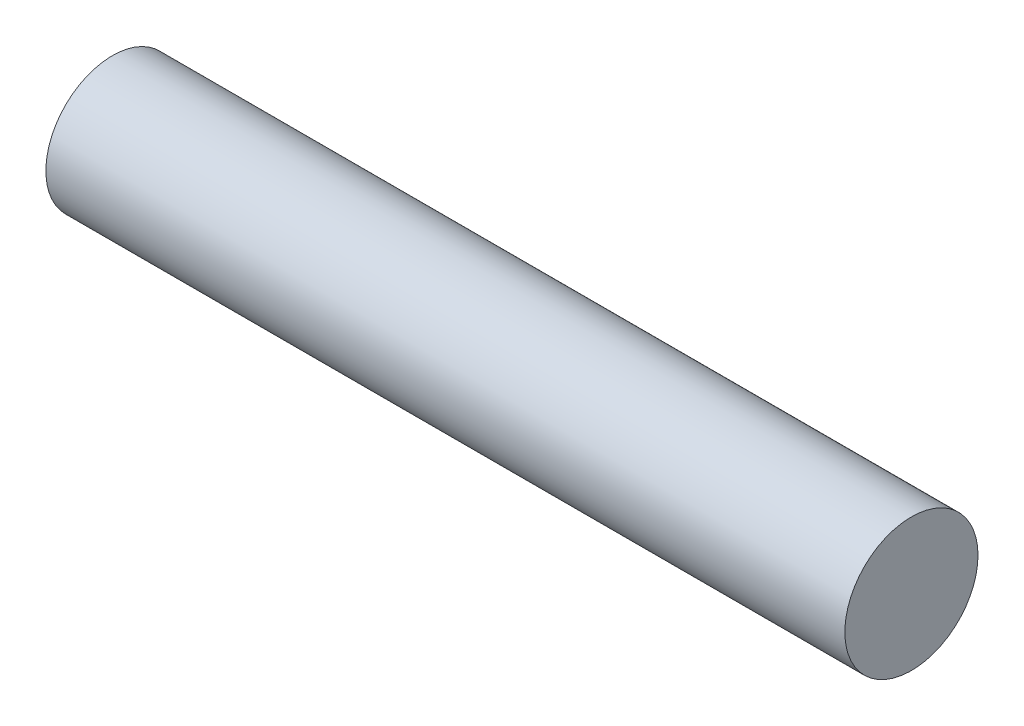
SolidWorks part; units mm, degrees
ref_plane "Front Plane" through (0, 0, 0) normal (0, 0, 1) x (1, 0, 0)
ref_plane "Top Plane" through (0, 0, 0) normal (0, 1, 0) x (1, 0, 0)
ref_plane "Right Plane" through (0, 0, 0) normal (1, 0, 0) x (0, 0, -1)
sketch "Sketch1" plane through (0, 0, 0) normal (1, 0, 0) x (0, 0, -1)
  circle A0 centre (0, 0) radius 0.5
  dimension "D1" = 1
extrude "Boss-Extrude1" add sketch "Sketch1" along normal blind 3 and the other way blind 3
